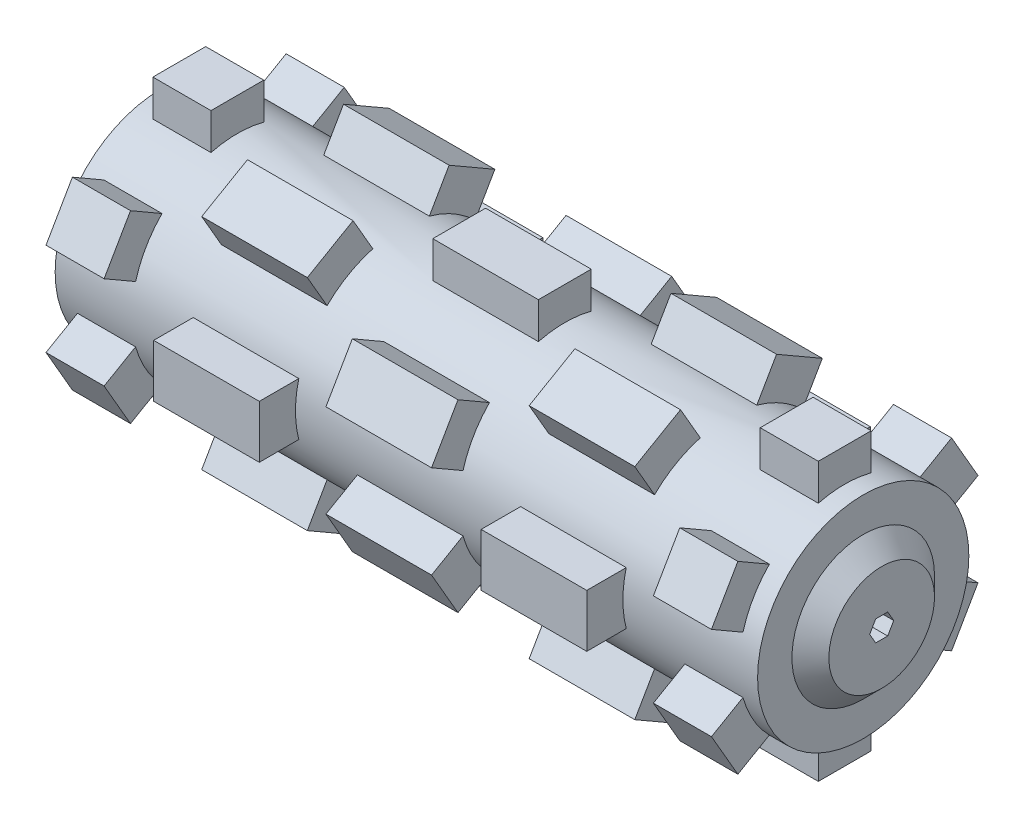
SolidWorks part; units mm, degrees
material "AISI 304"
ref_plane "Front Plane" through (0, 0, 0) normal (0, 0, 1) x (1, 0, 0)
ref_plane "Top Plane" through (0, 0, 0) normal (0, 1, 0) x (1, 0, 0)
ref_plane "Right Plane" through (0, 0, 0) normal (1, 0, 0) x (0, 0, -1)
sketch "Sketch1" plane through (0, 0, 0) normal (1, 0, 0) x (0, 0, -1)
  line L0 (0, -34.925) -> (0, 34.925) construction
  line L1 (-12.7, 66.675) -> (12.7, 66.675)
  line L2 (-12.7, 66.675) -> (-12.7, 34.925)
  line L3 (-12.7, 34.925) -> (12.7, 34.925)
  line L4 (12.7, 66.675) -> (12.7, 34.925)
  line L5 (-12.7, 66.675) -> (12.7, 34.925) construction
  line L6 (-12.7, 34.925) -> (12.7, 66.675) construction
  line L7 (51.3922, 44.336) -> (23.8959, 28.461)
  line L8 (51.3922, 44.336) -> (64.0922, 22.339)
  line L9 (64.0922, 22.339) -> (36.5959, 6.464)
  line L10 (23.8959, 28.461) -> (36.5959, 6.464)
  line L11 (64.0922, -22.339) -> (36.5959, -6.464)
  line L12 (64.0922, -22.339) -> (51.3922, -44.336)
  line L13 (51.3922, -44.336) -> (23.8959, -28.461)
  line L14 (36.5959, -6.464) -> (23.8959, -28.461)
  line L15 (12.7, -66.675) -> (12.7, -34.925)
  line L16 (12.7, -66.675) -> (-12.7, -66.675)
  line L17 (-12.7, -66.675) -> (-12.7, -34.925)
  line L18 (12.7, -34.925) -> (-12.7, -34.925)
  line L19 (-51.3922, -44.336) -> (-23.8959, -28.461)
  line L20 (-51.3922, -44.336) -> (-64.0922, -22.339)
  line L21 (-64.0922, -22.339) -> (-36.5959, -6.464)
  line L22 (-23.8959, -28.461) -> (-36.5959, -6.464)
  line L23 (-64.0922, 22.339) -> (-36.5959, 6.464)
  line L24 (-64.0922, 22.339) -> (-51.3922, 44.336)
  line L25 (-51.3922, 44.336) -> (-23.8959, 28.461)
  line L26 (-36.5959, 6.464) -> (-23.8959, 28.461)
  circle A0 centre (0, 0) radius 50.8
  point P3 (0, 50.8)
  point P10 (0, 0)
  point P14 (0, 0)
  point P34 (0, 0)
  dimension "D1" = 101.6
  dimension "D3" = 25.4
  dimension "D4" = 31.75
  dimension "D2" = 6
extrude "Boss-Extrude3" add sketch "Sketch1" along normal blind 50.8 contours A0 | L2 L1 L4 L3 | L23 L26 L25 L24 | L19 L22 L21 L20 | L15 L18 L17 L16 | L11 L14 L13 L12 | L7 L10 L9 L8
sketch "Sketch2" plane through (50.8, 0, 0) normal (1, 0, 0) x (0, 0, -1)
  circle A0 centre (0, 0) radius 50.8
extrude "Boss-Extrude4" add sketch "Sketch2" along normal blind 27.94
sketch "Sketch3" plane through (78.74, 0, 0) normal (1, 0, 0) x (0, 0, -1)
  line L0 (0, 0) -> (12.7, 66.675) construction
  line L1 (12.7, 66.675) -> (12.7, 49.1869) construction
  line L2 (36.4373, 12.7) -> (36.4373, 0)
  line L3 (51.3922, 44.336) -> (0, 0) construction
  line L4 (34.0936, 59.0519) -> (0, 0) construction
  line L5 (18.2186, 31.5556) -> (29.2172, 25.2056)
  line L6 (29.2172, 25.2056) -> (45.0922, 52.7019)
  line L7 (45.0922, 52.7019) -> (23.0951, 65.4019)
  line L8 (23.0951, 65.4019) -> (7.2201, 37.9056)
  line L9 (7.2201, 37.9056) -> (18.2186, 31.5556)
  line L10 (36.4373, 0) -> (36.4373, -12.7)
  line L11 (36.4373, -12.7) -> (68.1873, -12.7)
  line L12 (68.1873, -12.7) -> (68.1873, 12.7)
  line L13 (68.1873, 12.7) -> (36.4373, 12.7)
  line L14 (29.2172, -25.2056) -> (18.2186, -31.5556)
  line L15 (18.2186, -31.5556) -> (7.2201, -37.9056)
  line L16 (7.2201, -37.9056) -> (23.0951, -65.4019)
  line L17 (23.0951, -65.4019) -> (45.0922, -52.7019)
  line L18 (45.0922, -52.7019) -> (29.2172, -25.2056)
  line L19 (-7.2201, -37.9056) -> (-18.2186, -31.5556)
  line L20 (-18.2186, -31.5556) -> (-29.2172, -25.2056)
  line L21 (-29.2172, -25.2056) -> (-45.0922, -52.7019)
  line L22 (-45.0922, -52.7019) -> (-23.0951, -65.4019)
  line L23 (-23.0951, -65.4019) -> (-7.2201, -37.9056)
  line L24 (-36.4373, -12.7) -> (-36.4373, 0)
  line L25 (-36.4373, 0) -> (-36.4373, 12.7)
  line L26 (-36.4373, 12.7) -> (-68.1873, 12.7)
  line L27 (-68.1873, 12.7) -> (-68.1873, -12.7)
  line L28 (-68.1873, -12.7) -> (-36.4373, -12.7)
  line L29 (-29.2172, 25.2056) -> (-18.2186, 31.5556)
  line L30 (-18.2186, 31.5556) -> (-7.2201, 37.9056)
  line L31 (-7.2201, 37.9056) -> (-23.0951, 65.4019)
  line L32 (-23.0951, 65.4019) -> (-45.0922, 52.7019)
  line L33 (-45.0922, 52.7019) -> (-29.2172, 25.2056)
  circle A0 centre (0, 0) radius 50.8
  circle A1 centre (0, 0) radius 67.8737 construction
  point P44 (0, 0)
  dimension "D1" = 31.75
  dimension "D2" = 25.4
  dimension "D3" = 6
extrude "Boss-Extrude5" add sketch "Sketch3" along normal blind 50.8 contours A0 | L24 L25 L26 L27 L28 | L29 L30 L31 L32 L33 | L9 L5 L6 L7 L8 | L2 L10 L11 L12 L13 | L14 L15 L16 L17 L18 | L19 L20 L21 L22 L23
sketch "Sketch4" plane through (129.54, 0, 0) normal (1, 0, 0) x (0, 0, -1)
  circle A0 centre (0, 0) radius 50.8
extrude "Boss-Extrude6" add sketch "Sketch4" along normal blind 27.94
sketch "Sketch5" plane through (157.48, 0, 0) normal (1, 0, 0) x (0, 0, -1)
  line L0 (12.7, 66.675) -> (12.7, 49.1869) construction
  line L1 (-12.7, 66.675) -> (12.7, 66.675)
  line L2 (-12.7, 66.675) -> (-12.7, 34.925)
  line L3 (-12.7, 34.925) -> (12.7, 34.925)
  line L4 (12.7, 66.675) -> (12.7, 34.925)
  line L5 (51.3922, 44.336) -> (23.8959, 28.461)
  line L6 (51.3922, 44.336) -> (64.0922, 22.339)
  line L7 (64.0922, 22.339) -> (36.5959, 6.464)
  line L8 (23.8959, 28.461) -> (36.5959, 6.464)
  line L9 (64.0922, -22.339) -> (36.5959, -6.464)
  line L10 (64.0922, -22.339) -> (51.3922, -44.336)
  line L11 (51.3922, -44.336) -> (23.8959, -28.461)
  line L12 (36.5959, -6.464) -> (23.8959, -28.461)
  line L13 (12.7, -66.675) -> (12.7, -34.925)
  line L14 (12.7, -66.675) -> (-12.7, -66.675)
  line L15 (-12.7, -66.675) -> (-12.7, -34.925)
  line L16 (12.7, -34.925) -> (-12.7, -34.925)
  line L17 (-51.3922, -44.336) -> (-23.8959, -28.461)
  line L18 (-51.3922, -44.336) -> (-64.0922, -22.339)
  line L19 (-64.0922, -22.339) -> (-36.5959, -6.464)
  line L20 (-23.8959, -28.461) -> (-36.5959, -6.464)
  line L21 (-64.0922, 22.339) -> (-36.5959, 6.464)
  line L22 (-64.0922, 22.339) -> (-51.3922, 44.336)
  line L23 (-51.3922, 44.336) -> (-23.8959, 28.461)
  line L24 (-36.5959, 6.464) -> (-23.8959, 28.461)
  circle A0 centre (0, 0) radius 50.8
  point P33 (0, 0)
  dimension "D1" = 31.75
  dimension "D2" = 25.4
  dimension "D3" = 6
extrude "Boss-Extrude7" add sketch "Sketch5" along normal blind 27.94 contours A0 | L21 L24 L23 L22 | L2 L1 L4 L3 | L5 L8 L7 L6 | L17 L20 L19 L18 | L13 L16 L15 L14 | L9 L12 L11 L10
sketch "Sketch6" plane through (0, 0, 0) normal (-1, 0, 0) x (0, 0, 1)
  circle A0 centre (0, 0) radius 50.8
extrude "Boss-Extrude8" add sketch "Sketch6" along normal blind 27.94
sketch "Sketch7" plane through (-27.94, 0, 0) normal (-1, 0, 0) x (0, 0, 1)
  line L0 (23.0951, 65.4019) -> (45.0922, 52.7019)
  line L1 (45.0922, 52.7019) -> (29.2172, 25.2056)
  line L2 (29.2172, 25.2056) -> (7.2201, 37.9056)
  line L3 (7.2201, 37.9056) -> (23.0951, 65.4019)
  line L4 (36.4373, 12.7) -> (68.1873, 12.7)
  line L5 (68.1873, 12.7) -> (68.1873, -12.7)
  line L6 (68.1873, -12.7) -> (36.4373, -12.7)
  line L7 (36.4373, -12.7) -> (36.4373, 12.7)
  line L8 (29.2172, -25.2056) -> (45.0922, -52.7019)
  line L9 (45.0922, -52.7019) -> (23.0951, -65.4019)
  line L10 (23.0951, -65.4019) -> (7.2201, -37.9056)
  line L11 (7.2201, -37.9056) -> (29.2172, -25.2056)
  line L12 (-7.2201, -37.9056) -> (-23.0951, -65.4019)
  line L13 (-23.0951, -65.4019) -> (-45.0922, -52.7019)
  line L14 (-45.0922, -52.7019) -> (-29.2172, -25.2056)
  line L15 (-29.2172, -25.2056) -> (-7.2201, -37.9056)
  line L16 (-36.4373, -12.7) -> (-68.1873, -12.7)
  line L17 (-68.1873, -12.7) -> (-68.1873, 12.7)
  line L18 (-68.1873, 12.7) -> (-36.4373, 12.7)
  line L19 (-36.4373, 12.7) -> (-36.4373, -12.7)
  line L20 (-29.2172, 25.2056) -> (-45.0922, 52.7019)
  line L21 (-45.0922, 52.7019) -> (-23.0951, 65.4019)
  line L22 (-23.0951, 65.4019) -> (-7.2201, 37.9056)
  line L23 (-7.2201, 37.9056) -> (-29.2172, 25.2056)
  circle A0 centre (0, 0) radius 50.8
  point P28 (0, 0)
  dimension "D1" = 25.4
  dimension "D2" = 31.75
  dimension "D3" = 6
extrude "Boss-Extrude9" add sketch "Sketch7" along normal blind 50.8 contours L3 L0 L1 L2 | L20 L21 L22 L23 | A0 | L16 L17 L18 L19 | L12 L13 L14 L15 | L8 L9 L10 L11 | L4 L5 L6 L7
sketch "Sketch8" plane through (-78.74, 0, 0) normal (-1, 0, 0) x (0, 0, 1)
  circle A0 centre (0, 0) radius 50.8
extrude "Boss-Extrude10" add sketch "Sketch8" along normal blind 27.94
sketch "Sketch9" plane through (-106.68, 0, 0) normal (-1, 0, 0) x (0, 0, 1)
  line L0 (12.7, 66.675) -> (12.7, 49.1869) construction
  line L1 (-12.7, 66.675) -> (12.7, 66.675)
  line L2 (-12.7, 66.675) -> (-12.7, 34.925)
  line L3 (-12.7, 34.925) -> (12.7, 34.925)
  line L4 (12.7, 66.675) -> (12.7, 34.925)
  line L5 (51.3922, 44.336) -> (23.8959, 28.461)
  line L6 (51.3922, 44.336) -> (64.0922, 22.339)
  line L7 (64.0922, 22.339) -> (36.5959, 6.464)
  line L8 (23.8959, 28.461) -> (36.5959, 6.464)
  line L9 (64.0922, -22.339) -> (36.5959, -6.464)
  line L10 (64.0922, -22.339) -> (51.3922, -44.336)
  line L11 (51.3922, -44.336) -> (23.8959, -28.461)
  line L12 (36.5959, -6.464) -> (23.8959, -28.461)
  line L13 (12.7, -66.675) -> (12.7, -34.925)
  line L14 (12.7, -66.675) -> (-12.7, -66.675)
  line L15 (-12.7, -66.675) -> (-12.7, -34.925)
  line L16 (12.7, -34.925) -> (-12.7, -34.925)
  line L17 (-51.3922, -44.336) -> (-23.8959, -28.461)
  line L18 (-51.3922, -44.336) -> (-64.0922, -22.339)
  line L19 (-64.0922, -22.339) -> (-36.5959, -6.464)
  line L20 (-23.8959, -28.461) -> (-36.5959, -6.464)
  line L21 (-64.0922, 22.339) -> (-36.5959, 6.464)
  line L22 (-64.0922, 22.339) -> (-51.3922, 44.336)
  line L23 (-51.3922, 44.336) -> (-23.8959, 28.461)
  line L24 (-36.5959, 6.464) -> (-23.8959, 28.461)
  circle A0 centre (0, 0) radius 50.8
  point P33 (0, 0)
  dimension "D1" = 31.75
  dimension "D2" = 25.4
  dimension "D3" = 6
extrude "Boss-Extrude11" add sketch "Sketch9" along normal blind 27.94 contours A0 | L21 L24 L23 L22 | L17 L20 L19 L18 | L13 L16 L15 L14 | L9 L12 L11 L10 | L5 L8 L7 L6 | L2 L1 L4 L3
sketch "Sketch10" plane through (185.42, 0, 0) normal (1, 0, 0) x (0, 0, -1)
  circle A0 centre (0, 0) radius 50.8
extrude "Boss-Extrude12" add sketch "Sketch10" along normal blind 8.89
sketch "Sketch11" plane through (-134.62, 0, 0) normal (-1, 0, 0) x (0, 0, 1)
  circle A0 centre (0, 0) radius 50.8
extrude "Boss-Extrude13" add sketch "Sketch11" along normal blind 8.89
sketch "Sketch12" plane through (194.31, 0, 0) normal (1, 0, 0) x (0, 0, -1)
  circle A1 centre (0, 0) radius 25.4
  dimension "D2" = 50.8
extrude "Boss-Extrude14" add sketch "Sketch12" along normal blind 8.89
sketch "Sketch13" plane through (-143.51, 0, 0) normal (-1, 0, 0) x (0, 0, 1)
  circle A0 centre (0, 0) radius 25.4
  dimension "D1" = 50.8
extrude "Boss-Extrude15" add sketch "Sketch13" along normal blind 8.89
sketch "Sketch14" plane through (-152.4, 0, 0) normal (-1, 0, 0) x (0, 0, 1)
  line L1 (5.7735, 0) -> (2.8868, 5)
  line L2 (2.8868, 5) -> (-2.8868, 5)
  line L3 (-2.8868, 5) -> (-5.7735, 0)
  line L4 (-5.7735, 0) -> (-2.8868, -5)
  line L5 (-2.8868, -5) -> (2.8868, -5)
  line L6 (2.8868, -5) -> (5.7735, 0)
  circle A0 centre (0, 0) radius 5
  circle A1 centre (0, 0) radius 5 construction
  dimension "D1" = 10
extrude "Cut-Extrude1" cut sketch "Sketch14" against normal through all contours A0 L3 L4 | A0 | A0 L2 L3 | A0 L1 L2 | A0 L6 L1 | A0 L5 L6 | A0 L4 L5 region at (-152.4, 0, 5.1678) region at (-152.4, 4.4755, 2.5839) region at (-152.4, 0, 0) region at (-152.4, -4.4755, 2.5839) region at (-152.4, 4.4755, -2.5839) region at (-152.4, -4.4755, -2.5839) region at (-152.4, 0, -5.1678)
chamfer "Chamfer3" distance 8.89 angle 45 2 edges at (-143.51, 0, 25.4) (194.31, 0, -25.4)
